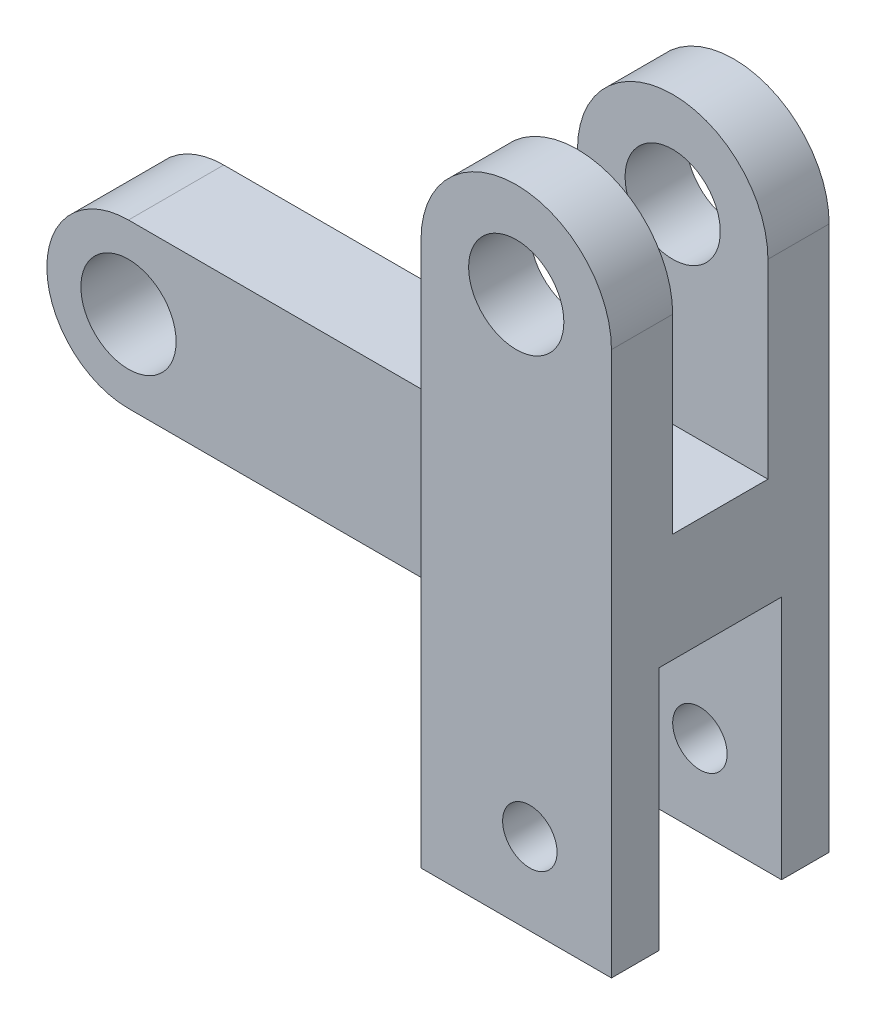
SolidWorks part; units mm, degrees
ref_plane "前视基准面" through (0, 0, 0) normal (0, 0, 1) x (1, 0, 0)
ref_plane "上视基准面" through (0, 0, 0) normal (0, 1, 0) x (1, 0, 0)
ref_plane "右视基准面" through (0, 0, 0) normal (1, 0, 0) x (0, 0, -1)
other "Configuration Table"
sketch "草图1" plane through (0, 0, 0) normal (0, 1, 0) x (1, 0, 0)
  line L1 (0, 3.5) -> (7, 3.5)
  line L2 (0, -3.5) -> (7, -3.5)
  line L3 (0, 3.5) -> (7, 3.5) construction
  line L4 (7, 3.5) -> (7, -3.5)
  line L5 (0, 3.5) -> (0, -3.5)
  dimension "D1" = 7
  dimension "D4" = 90
  dimension "D5" = 7
extrude "凸台-拉伸1" add sketch "草图1" along normal blind 2.4
sketch "草图10" plane through (0, 0, -3.5) normal (0, 0, -1) x (-1, 0, 0)
  line L3 (-7, 2.4) -> (0, 2.4) construction
  line L6 (-7, 2.4) -> (0, 2.4)
  line L7 (0, 2.4) -> (0, 10)
  line L9 (-7, 10) -> (-7, 2.4)
  line L10 (0, 2.4) -> (0, 0) construction
  arc A1 (0, 10) -> (-7, 10) centre (-3.5, 10) ccw
  line M3 (0, 2.4) -> (-7, 2.4)
  dimension "D8" = 3.5
  dimension "D9" = 10
extrude "凸台-拉伸6" add sketch "草图10" against normal blind 1.75 contours L7 A1 L9 M3 region at (3.5, 7.6039, -3.5)
extrude "凸台-拉伸8" add sketch "草图10<2>" along normal blind 1.75 from offset 7 contours L7 A1 L9 M3 region at (3.5, 7.6039, -3.5) offset against normal yes
sketch "草图10<2>" plane through (0, 0, -3.5) normal (0, 0, -1) x (-1, 0, 0) same geometry as "草图10"
sketch "草图11" plane through (0, 0, -3.5) normal (0, 0, -1) x (-1, 0, 0)
  circle A2 centre (-3.5, 10) radius 1.75
  dimension "D3" = 3.5
extrude "切除-拉伸1" cut sketch "草图11" against normal through all
sketch "草图17" plane through (0, 0, 0) normal (0, -1, 0) x (1, 0, 0)
  line L6 (0, 3.5) -> (0, -3.5)
  line L7 (0, -3.5) -> (7, -3.5)
  line L8 (7, -3.5) -> (7, 3.5)
  line L9 (7, 3.5) -> (0, 3.5)
  line L12 (0, 3.5) -> (0, -3.5)
  line L13 (0, -3.5) -> (7, -3.5)
  line L14 (7, -3.5) -> (7, 3.5)
  line L15 (7, 3.5) -> (0, 3.5)
  dimension "D1" = 0
extrude "凸台-拉伸10" add sketch "草图17" along normal blind 10
sketch "草图15" plane through (0, 0, 0) normal (0, 0, 1) x (1, 0, 0)
  line L2 (7, 3) -> (7, -3)
  line L10 (7, 10) -> (7, -10) construction
  line L14 (-13, 3) -> (7, 3)
  line L15 (7, 10) -> (7, -10) construction
  line L17 (7, 2.4) -> (7.3779, 2.4)
  line L18 (0, 2.4) -> (7, 2.4) construction
  line L19 (-13, -3) -> (7, -3)
  line L20 (7, -10) -> (0, -10) construction
  arc A0 (-13, -3) -> (-13, 3) centre (-13, 0) cw
  circle A1 centre (-13, 0) radius 1.75
  dimension "D3" = 3.5
  dimension "D1" = 3
  dimension "D2" = 7
  dimension "D4" = 20
extrude "凸台-拉伸9" add sketch "草图15" along normal mid plane 3.5 contours A0 L19 L2 L14 A1 region at (-3.5072, 0, 0)
sketch "草图12" plane through (0, 4, 3.5) normal (0, 0, -1) x (1, 0, 0)
  line L0 (0, 14) -> (7, 14) construction
  line L2 (7, -6) -> (7, 14) construction
  circle A0 centre (4, 11) radius 1
  dimension "D2" = 2
  dimension "D1" = 3
  dimension "D3" = 3
extrude "切除-拉伸2" cut sketch "草图12" along normal through all
sketch "草图18" plane through (7.4, -10, 0) normal (0, 1, 0) x (1, 0, 0)
  line L0 (-0.4, 1.75) -> (-0.4, 3.5) construction
  line L11 (-7.4, -2.25) -> (-0.4, -2.25)
  line L12 (-7.4, -2.25) -> (-7.4, 2.25)
  line L13 (-7.4, 2.25) -> (-0.4, 2.25)
  line L14 (-0.4, -2.25) -> (-0.4, 2.25)
  point P4 (-7.4, 0)
  dimension "D1" = 4.5
  dimension "D2" = 7
extrude "切除-拉伸4" cut sketch "草图18" along normal blind 9
sketch "草图19" plane through (0, 0, 3.5) normal (0, 0, 1) x (1, 0, 0)
  line L4 (0, 10) -> (0, -10)
  line L5 (0, -10) -> (7, -10)
  line L6 (7, -10) -> (7, 10)
  line L8 (0, 10) -> (0, -10)
  line L9 (0, -10) -> (7, -10)
  line L10 (7, -10) -> (7, 10)
  circle A0 centre (4, -7) radius 1 construction
  circle A1 centre (4, -7) radius 1
  circle A2 centre (3.5, 10) radius 1.75 construction
  arc A3 (7, 10) -> (0, 10) centre (3.5, 10) ccw
  arc A4 (7, 10) -> (0, 10) centre (3.5, 10) ccw
  circle A5 centre (3.5, 10) radius 1.75
  dimension "D1" = 0
extrude "凸台-拉伸11" add sketch "草图19" along normal blind 0.5
sketch "草图20" plane through (0, 0, -3.5) normal (0, 0, -1) x (-1, 0, 0)
  line L4 (-7, 10) -> (-7, -10)
  line L5 (-7, -10) -> (0, -10)
  line L6 (0, -10) -> (0, 10)
  line L8 (-7, 10) -> (-7, -10)
  line L9 (-7, -10) -> (0, -10)
  line L10 (0, -10) -> (0, 10)
  circle A0 centre (-4, -7) radius 1 construction
  circle A1 centre (-4, -7) radius 1
  circle A2 centre (-3.5, 10) radius 1.75 construction
  arc A3 (0, 10) -> (-7, 10) centre (-3.5, 10) ccw
  arc A4 (0, 10) -> (-7, 10) centre (-3.5, 10) ccw
  circle A5 centre (-3.5, 10) radius 1.75
  dimension "D1" = 0
extrude "凸台-拉伸12" add sketch "草图20" along normal blind 0.5
